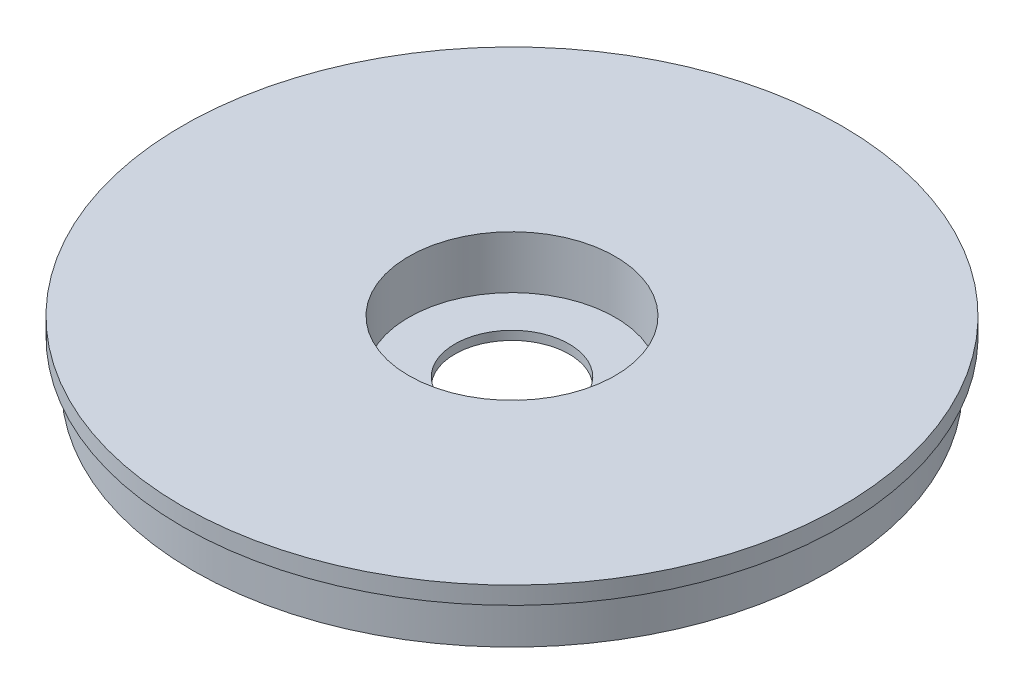
SolidWorks part; units mm, degrees
ref_plane "Płaszczyzna przednia" through (0, 0, 0) normal (0, 0, 1) x (1, 0, 0)
ref_plane "Płaszczyzna górna" through (0, 0, 0) normal (0, 1, 0) x (1, 0, 0)
ref_plane "Płaszczyzna prawa" through (0, 0, 0) normal (1, 0, 0) x (0, 0, -1)
sketch "Szkic4" plane through (0, 0, 0) normal (0, 1, 0) x (1, 0, 0)
  circle A0 centre (0, 0) radius 75
extrude "Dodanie-wyciągnięcie2" add sketch "Szkic4" along normal blind 14
sketch "Szkic5" plane through (0, 14, 0) normal (0, 1, 0) x (1, 0, 0)
  circle A0 centre (0, 0) radius 23.5
extrude "Wytnij-wyciągnięcie3" cut sketch "Szkic5" against normal blind 12
sketch "Szkic6" plane through (0, 2, 0) normal (0, 1, 0) x (1, 0, 0)
  circle A0 centre (0, 0) radius 13
  dimension "D1" = 26
extrude "Wytnij-wyciągnięcie4" cut sketch "Szkic6" against normal blind 12
sketch "Szkic7" plane through (0, 0, 0) normal (0, -1, 0) x (1, 0, 0)
  circle A0 centre (0, 0) radius 75
  circle A1 centre (0, 0) radius 72.5
  circle A2 centre (0, 0) radius 75 construction
  dimension "D1" = 2.5
extrude "Wytnij-wyciągnięcie5" cut sketch "Szkic7" against normal blind 10
